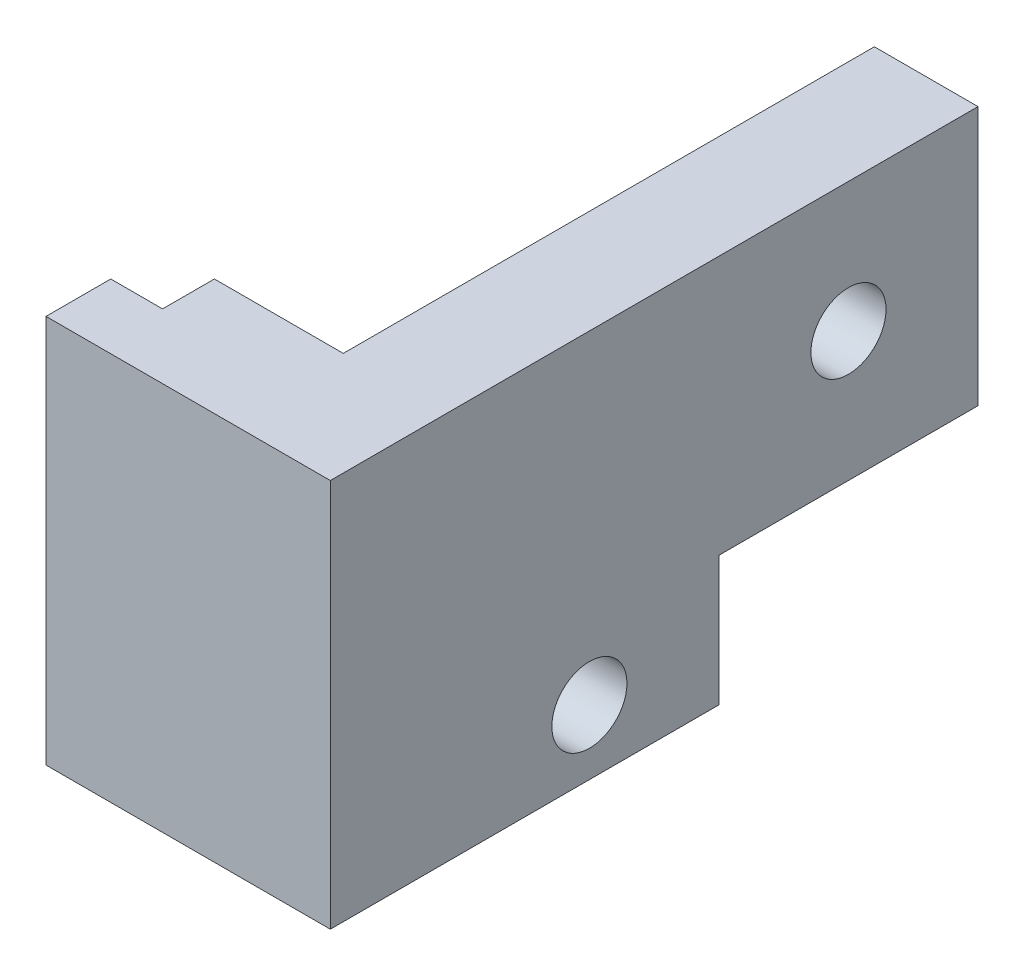
SolidWorks part; units mm, degrees
ref_plane "前视基准面" through (0, 0, 0) normal (0, 0, 1) x (1, 0, 0)
ref_plane "上视基准面" through (0, 0, 0) normal (0, 1, 0) x (1, 0, 0)
ref_plane "右视基准面" through (0, 0, 0) normal (1, 0, 0) x (0, 0, -1)
other "Configuration Table"
sketch "草图1" plane through (0, 0, 0) normal (0, 0, 1) x (1, 0, 0)
  line L1 (0, 0) -> (-40, 0)
  line L2 (0, 0) -> (0, 30)
  line L3 (0, 30) -> (-40, 30)
  line L4 (-40, 0) -> (-40, 30)
  dimension "D1" = 40
  dimension "D2" = 30
extrude "凸台-拉伸1" add sketch "草图1" along normal blind 5
sketch "草图2" plane through (-40, 0, 0) normal (-1, 0, 0) x (0, 0, 1)
  line L4 (0, 30) -> (0, 0)
  line L5 (0, 0) -> (5, 0)
  line L6 (5, 0) -> (5, 30)
  line L7 (5, 30) -> (0, 30)
  line L8 (0, 30) -> (0, 0)
  line L9 (0, 0) -> (5, 0)
  line L10 (5, 0) -> (5, 30)
  line L11 (5, 30) -> (0, 30)
  dimension "D1" = 0
extrude "凸台-拉伸2" add sketch "草图2" along normal blind 20
sketch "草图3" plane through (0, 0, 0) normal (0, 0, -1) x (-1, 0, 0)
  line L0 (60, 0) -> (0, 0) construction
  line L1 (60, 30) -> (40, 30) construction
  line L2 (60, 30) -> (60, 0) construction
  line L3 (60, 0) -> (40, 0) construction
  line L4 (40, 30) -> (40, 0) construction
  line L5 (30, 30) -> (30, 0) construction
  line L6 (0, 30) -> (60, 30) construction
  line L7 (0, 0) -> (20, 0)
  line L8 (20, 30) -> (20, 0)
  line L9 (0, 30) -> (20, 30)
  line L10 (0, 30) -> (0, 0)
  dimension "D1" = 20
extrude "凸台-拉伸3" add sketch "草图3" along normal blind 5
sketch "草图4" plane through (0, 0, 5) normal (0, 0, 1) x (1, 0, 0)
  line L0 (0, 30) -> (-60, 30) construction
  line L1 (-60, 30) -> (-45, 30) construction
  line L2 (-60, 30) -> (-60, 0) construction
  line L3 (-60, 0) -> (-45, 0) construction
  line L4 (-45, 30) -> (-45, 0) construction
  line L5 (-60, 0) -> (0, 0) construction
  line L6 (-60, 0) -> (-60, 30) construction
  line L7 (-30, 30) -> (-30, -4.6416) construction
  line L8 (0, 0) -> (-15, 0)
  line L9 (-15, 30) -> (-15, 0)
  line L10 (0, 30) -> (-15, 30)
  line L11 (0, 30) -> (0, 0)
  dimension "D1" = 0
  dimension "D2" = 15
extrude "切除-拉伸1" cut sketch "草图4" against normal blind 5
sketch "草图6" plane through (0, 0, 0) normal (0, 0, 1) x (1, 0, 0)
  line L0 (-7.5, 30) -> (-7.5, 25) construction
  line L1 (0, 30) -> (-15, 30) construction
  line L2 (-7.5, 25) -> (-7.5, 5) construction
  circle A0 centre (-7.5, 25) radius 1.5
  circle A1 centre (-7.5, 5) radius 1.5
  dimension "D3" = 3
  dimension "D4" = 3
  dimension "D1" = 5
  dimension "D2" = 20
extrude "切除-拉伸3" cut sketch "草图6" against normal blind 5
sketch "草图7" plane through (0, 0, 0) normal (0, 0, 1) x (1, 0, 0)
  line L4 (0, 0) -> (0, 30)
  line L5 (0, 30) -> (-15, 30)
  line L6 (-15, 30) -> (-15, 0)
  line L7 (-15, 0) -> (0, 0)
  line L8 (0, 0) -> (0, 30)
  line L9 (0, 30) -> (-15, 30)
  line L10 (-15, 30) -> (-15, 0)
  line L11 (-15, 0) -> (0, 0)
  dimension "D1" = 0
extrude "切除-拉伸4" cut sketch "草图7" against normal up to surface (5 mm away) up to face at (-6, 25, -5)
sketch "草图8" plane through (0, 0, -5) normal (0, 0, -1) x (-1, 0, 0)
  line L4 (15, 30) -> (15, 0)
  line L5 (15, 0) -> (20, 0)
  line L6 (20, 0) -> (20, 30)
  line L7 (20, 30) -> (15, 30)
  line L8 (15, 30) -> (15, 0)
  line L9 (15, 0) -> (20, 0)
  line L10 (20, 0) -> (20, 30)
  line L11 (20, 30) -> (15, 30)
  dimension "D1" = 0
extrude "凸台-拉伸4" add sketch "草图8" along normal blind 20
sketch "草图9" plane through (-15, 0, 0) normal (1, 0, 0) x (0, 0, -1)
  line L4 (-5, 30) -> (-5, 0)
  line L5 (-5, 0) -> (25, 0)
  line L6 (25, 0) -> (25, 30)
  line L7 (25, 30) -> (-5, 30)
  line L8 (-5, 30) -> (-5, 0)
  line L9 (-5, 0) -> (25, 0)
  line L10 (25, 0) -> (25, 30)
  line L11 (25, 30) -> (-5, 30)
  dimension "D1" = 0
extrude "凸台-拉伸5" add sketch "草图9" along normal blind 3
sketch "草图10" plane through (-12, 0, 0) normal (1, 0, 0) x (0, 0, -1)
  line L0 (25, 30) -> (15, 30) construction
  line L1 (25, 30) -> (-5, 30) construction
  line L2 (15, 30) -> (15, 5) construction
  circle A0 centre (15, 5) radius 1.5
  dimension "D3" = 3
  dimension "D1" = 10
  dimension "D2" = 25
extrude "切除-拉伸5" cut sketch "草图10" against normal blind 13
sketch "草图11" plane through (-12, 0, 0) normal (1, 0, 0) x (0, 0, -1)
  circle A0 centre (15, 5) radius 2.9
  dimension "D1" = 5.8
extrude "切除-拉伸6" cut sketch "草图11" against normal offset from surface (6 mm away) 2 up to face at (-20, 5, -16.5)
sketch "草图12" plane through (0, 0, -25) normal (0, 0, -1) x (-1, 0, 0)
  line L1 (20, 30) -> (12, 30)
  line L2 (20, 30) -> (20, 10)
  line L3 (20, 10) -> (12, 10)
  line L4 (12, 30) -> (12, 10)
  dimension "D1" = 20
extrude "凸台-拉伸6" add sketch "草图12" along normal blind 20
sketch "草图13" plane through (-20, 0, 0) normal (-1, 0, 0) x (0, 0, 1)
  line L0 (-45, 10) -> (-45, 30) construction
  line L1 (-45, 17) -> (-25, 17)
  line L2 (-45, 17) -> (-45, 10)
  line L3 (-45, 10) -> (-25, 10)
  line L6 (-25, 0) -> (-18, 0)
  line L7 (-25, 0) -> (-25, 10)
  line L8 (-25, 17) -> (-18, 17)
  line L9 (-18, 0) -> (-18, 17)
  dimension "D1" = 7
  dimension "D2" = 7
extrude "切除-拉伸7" cut sketch "草图13" against normal blind 4.2
sketch "草图14" plane through (-12, 0, 0) normal (1, 0, 0) x (0, 0, -1)
  line L0 (45, 30) -> (45, 20) construction
  line L1 (45, 30) -> (45, 10) construction
  line L2 (45, 20) -> (35, 20) construction
  circle A0 centre (35, 20) radius 1.5
  dimension "D2" = 3
  dimension "D1" = 10
extrude "切除-拉伸8" cut sketch "草图14" against normal blind 14.2
sketch "草图15" plane through (-12, 0, 0) normal (1, 0, 0) x (0, 0, -1)
  circle A0 centre (35, 20) radius 2.9
  dimension "D1" = 5.8
extrude "切除-拉伸9" cut sketch "草图15" against normal offset from surface (6 mm away) 2 up to face at (-20, 20, -36.5)
sketch "草图16" plane through (-20, 0, 0) normal (-1, 0, 0) x (0, 0, 1)
  line L0 (-18, 0) -> (0, 0) construction
  line L1 (0, 30) -> (-4, 30)
  line L2 (0, 30) -> (0, 0)
  line L3 (0, 0) -> (-4, 0)
  line L4 (-4, 30) -> (-4, 0)
  dimension "D1" = 4
extrude "凸台-拉伸7" add sketch "草图16" along normal blind 9.95
sketch "草图17" plane through (-60, 0, 0) normal (-1, 0, 0) x (0, 0, 1)
  line L4 (5, 30) -> (0, 30)
  line L5 (0, 30) -> (0, 0)
  line L6 (0, 0) -> (5, 0)
  line L7 (5, 0) -> (5, 30)
  line L8 (5, 30) -> (0, 30)
  line L9 (0, 30) -> (0, 0)
  line L10 (0, 0) -> (5, 0)
  line L11 (5, 0) -> (5, 30)
  dimension "D1" = 0
extrude "切除-拉伸10" cut sketch "草图17" against normal offset from surface (26.05 mm away) 4 up to face at (-29.95, 15, -2)
